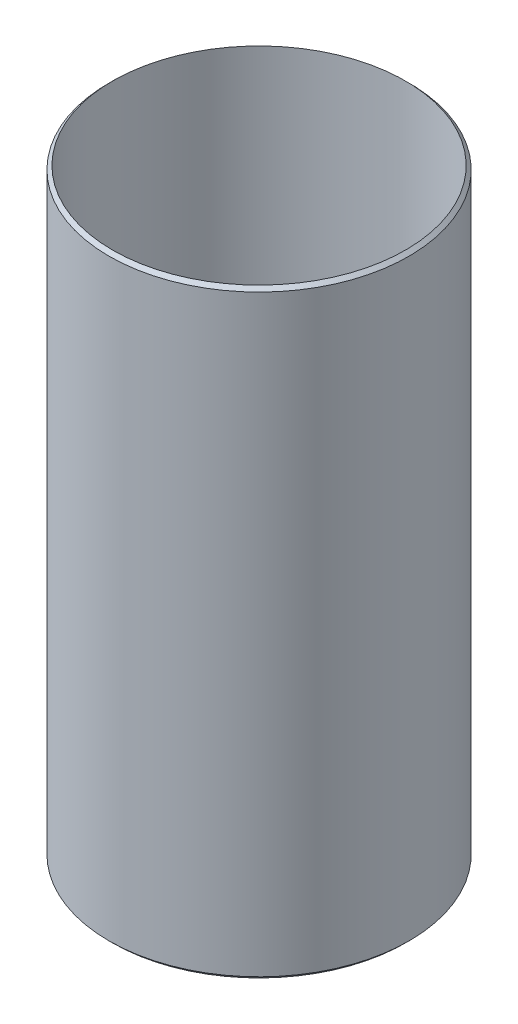
SolidWorks part; units mm, degrees
material "Plain Carbon Steel"
ref_plane "Front Plane" through (0, 0, 0) normal (0, 0, 1) x (1, 0, 0)
ref_plane "Top Plane" through (0, 0, 0) normal (0, 1, 0) x (1, 0, 0)
ref_plane "Right Plane" through (0, 0, 0) normal (1, 0, 0) x (0, 0, -1)
sketch "Sketch1" plane through (0, 0, 0) normal (0, 1, 0) x (1, 0, 0)
  circle A0 centre (0, 0) radius 83
  circle A1 centre (0, 0) radius 85
  dimension "D1" = 170
  dimension "D2" = 2
extrude "Boss-Extrude1" add sketch "Sketch1" along normal blind 340
chamfer "Chamfer1" distance 2 angle 45 2 edges at (0, 0, 85) (0, 340, 85)
equation "\"TubeDiameter\" = 6.6929in"
